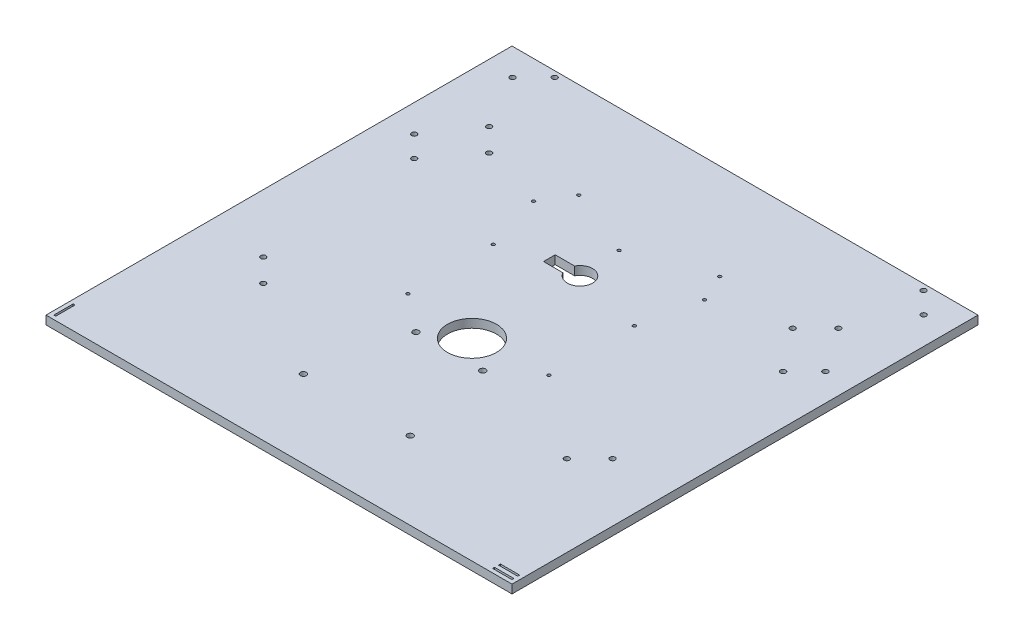
SolidWorks part; units mm, degrees
material "Acrylic (Medium-high impact)"
ref_plane "Front Plane" through (0, 0, 0) normal (0, 0, 1) x (1, 0, 0)
ref_plane "Top Plane" through (0, 0, 0) normal (0, 1, 0) x (1, 0, 0)
ref_plane "Right Plane" through (0, 0, 0) normal (1, 0, 0) x (0, 0, -1)
sketch "Sketch2" plane through (0, 0, 0) normal (0, 1, 0) x (1, 0, 0)
  line L1 (0, 0) -> (304.8, 0)
  line L2 (0, 0) -> (0, 304.8)
  line L3 (0, 304.8) -> (304.8, 304.8)
  line L4 (304.8, 0) -> (304.8, 304.8)
  dimension "D1" = 304.8
  dimension "D2" = 304.8
extrude "Boss-Extrude1" add sketch "Sketch2" along normal blind 5.588
sketch "Sketch4" plane through (0, 5.588, 0) normal (0, 1, 0) x (1, 0, 0)
  line L0 (0, 304.8) -> (0, 0) construction
  line L1 (2.54, 2.54) -> (3.81, 2.54)
  line L2 (2.54, 2.54) -> (2.54, 15.24)
  line L3 (2.54, 15.24) -> (3.81, 15.24)
  line L4 (3.81, 2.54) -> (3.81, 15.24)
  line L5 (2.54, 302.26) -> (3.81, 302.26) construction
  line L6 (2.54, 302.26) -> (2.54, 289.56) construction
  line L7 (2.54, 289.56) -> (3.81, 289.56) construction
  line L8 (3.81, 302.26) -> (3.81, 289.56) construction
  line L9 (6.35, 302.26) -> (7.62, 302.26) construction
  line L10 (6.35, 302.26) -> (6.35, 289.56) construction
  line L11 (6.35, 289.56) -> (7.62, 289.56) construction
  line L12 (7.62, 302.26) -> (7.62, 289.56) construction
  line L13 (304.8, 304.8) -> (0, 304.8) construction
  line L14 (0, 0) -> (304.8, 0) construction
  line L15 (304.8, 0) -> (304.8, 304.8) construction
  line L16 (302.26, 2.54) -> (289.56, 2.54)
  line L17 (302.26, 2.54) -> (302.26, 3.81)
  line L18 (302.26, 3.81) -> (289.56, 3.81)
  line L19 (289.56, 2.54) -> (289.56, 3.81)
  line L20 (302.26, 6.35) -> (289.56, 6.35)
  line L21 (302.26, 6.35) -> (302.26, 7.62)
  line L22 (302.26, 7.62) -> (289.56, 7.62)
  line L23 (289.56, 6.35) -> (289.56, 7.62)
  dimension "D1" = 12.7
  dimension "D2" = 1.27
  dimension "D3" = 2.54
  dimension "D4" = 2.54
  dimension "D5" = 2.54
  dimension "D6" = 2.54
  dimension "D7" = 2.54
  dimension "D8" = 2.54
  dimension "D9" = 2.54
  dimension "D10" = 2.54
extrude "Cut-Extrude1" cut sketch "Sketch4" against normal through all
sketch "Sketch5" plane through (0, 5.588, 0) normal (0, 1, 0) x (1, 0, 0)
  line L0 (0, 304.8) -> (0, 0) construction
  line L1 (34.5465, 268.1122) -> (263.4005, 268.1122)
  line L2 (34.5465, 268.1122) -> (34.5465, 281.0662)
  line L3 (34.5465, 281.0662) -> (263.4005, 281.0662)
  line L4 (263.4005, 268.1122) -> (263.4005, 281.0662)
  line L5 (304.8, 0) -> (304.8, 304.8) construction
  line L6 (304.8, 304.8) -> (0, 304.8) construction
  dimension "D1" = 34.5465
  dimension "D2" = 41.3995
  dimension "D3" = 23.7338
  dimension "D4" = 12.954
extrude "Cut-Extrude2" cut sketch "Sketch5" against normal blind 0.254
sketch "Sketch6" plane through (0, 5.588, 0) normal (0, 1, 0) x (1, 0, 0)
  circle A0 centre (152.48, 126.1263) radius 15.748 construction
  circle A1 centre (152.48, 126.1263) radius 15.748 construction
  circle A2 centre (152.48, 126.1263) radius 16.002
  circle A3 centre (31.75, 300.9596) radius 1.7 construction
  circle A4 centre (17.9388, 287.1483) radius 1.7 construction
  circle A5 centre (273.05, 300.9596) radius 1.7 construction
  circle A6 centre (286.8613, 287.1483) radius 1.7 construction
  circle A7 centre (286.8613, 222.9066) radius 1.7 construction
  circle A8 centre (273.05, 209.0954) radius 1.7 construction
  circle A9 centre (31.75, 209.0954) radius 1.7 construction
  circle A10 centre (17.9388, 222.9066) radius 1.7 construction
  circle A11 centre (31.75, 300.9596) radius 1.7
  circle A12 centre (17.9388, 287.1483) radius 1.7
  circle A13 centre (273.05, 300.9596) radius 1.7
  circle A14 centre (286.8613, 287.1483) radius 1.7
  circle A15 centre (286.8613, 222.9066) radius 1.7
  circle A16 centre (273.05, 209.0954) radius 1.7
  circle A17 centre (31.75, 209.0954) radius 1.7
  circle A18 centre (17.9388, 222.9066) radius 1.7
  circle A19 centre (38.1788, 103.933) radius 1.7 construction
  circle A20 centre (53.133, 88.9788) radius 1.7 construction
  circle A21 centre (251.667, 88.9788) radius 1.7 construction
  circle A22 centre (266.6212, 103.933) radius 1.7 construction
  circle A23 centre (266.6212, 251.667) radius 1.7 construction
  circle A24 centre (251.667, 236.7127) radius 1.7 construction
  circle A25 centre (53.133, 236.7127) radius 1.7 construction
  circle A26 centre (38.1788, 251.667) radius 1.7 construction
  circle A27 centre (38.1788, 103.933) radius 1.7
  circle A28 centre (53.133, 88.9788) radius 1.7
  circle A29 centre (251.667, 88.9788) radius 1.7
  circle A30 centre (266.6212, 103.933) radius 1.7
  circle A31 centre (266.6212, 251.667) radius 1.7
  circle A32 centre (251.667, 236.7127) radius 1.7
  circle A33 centre (53.133, 236.7127) radius 1.7
  circle A34 centre (38.1788, 251.667) radius 1.7
  circle A35 centre (117.555, 50.8216) radius 4.5 construction
  circle A36 centre (187.405, 50.8216) radius 4.5 construction
  circle A37 centre (174.3081, 111.328) radius 4.5 construction
  circle A38 centre (130.6519, 111.328) radius 4.5 construction
  circle A39 centre (117.555, 50.8216) radius 4.5 construction
  circle A40 centre (187.405, 50.8216) radius 4.5 construction
  circle A41 centre (174.3081, 111.328) radius 4.5 construction
  circle A42 centre (130.6519, 111.328) radius 4.5 construction
  circle A43 centre (130.6519, 111.328) radius 1.96
  circle A44 centre (174.3081, 111.328) radius 1.96
  circle A45 centre (187.405, 50.8216) radius 1.96
  circle A46 centre (117.555, 50.8216) radius 1.96
  dimension "D1" = 0.254
  dimension "D2" = 2.54
extrude "Cut-Extrude3" cut sketch "Sketch6" against normal through all
sketch "Sketch7" plane through (0, 5.588, 0) normal (0, 1, 0) x (1, 0, 0)
  line L0 (152.4, 304.8) -> (152.4, 0) construction
  line L1 (304.8, 304.8) -> (0, 304.8) construction
  line L2 (0, 0) -> (304.8, 0) construction
  line L4 (145.0768, 200.66) -> (132.3768, 200.66)
  line L5 (145.0768, 200.66) -> (145.0768, 193.04) construction
  line L6 (145.0768, 193.04) -> (132.3768, 193.04)
  line L7 (132.3768, 200.66) -> (132.3768, 193.04)
  circle A0 centre (152.4, 196.85) radius 8.255 construction
  arc A1 (145.0768, 200.66) -> (145.0768, 193.04) centre (152.4, 196.85) cw
  dimension "D2" = 16.51
  dimension "D1" = 107.95
  dimension "D3" = 7.62
  dimension "D4" = 12.7
extrude "Cut-Extrude4" cut sketch "Sketch7" against normal through all
sketch "Sketch8" plane through (0, 5.588, 0) normal (0, 1, 0) x (1, 0, 0)
  circle A0 centre (94.94, 223.995) radius 0.762 construction
  circle A1 centre (150.82, 223.995) radius 0.762 construction
  circle A2 centre (206.7, 223.995) radius 0.762 construction
  circle A3 centre (94.94, 223.995) radius 0.762 construction
  circle A4 centre (150.82, 223.995) radius 0.762 construction
  circle A5 centre (206.7, 223.995) radius 0.762 construction
  circle A6 centre (206.7, 223.995) radius 1.016
  circle A7 centre (150.82, 223.995) radius 1.016
  circle A8 centre (94.94, 223.995) radius 1.016
  dimension "D1" = 0.254
extrude "Cut-Extrude5" cut sketch "Sketch8" against normal through all
sketch "Sketch9" plane through (0, 5.588, 0) normal (0, 1, 0) x (1, 0, 0)
  circle A0 centre (106.3, 242.18) radius 0.762 construction
  circle A1 centre (106.3, 186.3) radius 0.762 construction
  circle A2 centre (106.3, 130.42) radius 0.762 construction
  circle A3 centre (198.5, 130.42) radius 0.762 construction
  circle A4 centre (198.5, 186.3) radius 0.762 construction
  circle A5 centre (198.5, 242.18) radius 0.762 construction
  circle A6 centre (106.3, 242.18) radius 0.762 construction
  circle A7 centre (106.3, 186.3) radius 0.762 construction
  circle A8 centre (106.3, 130.42) radius 0.762 construction
  circle A9 centre (198.5, 130.42) radius 0.762 construction
  circle A10 centre (198.5, 186.3) radius 0.762 construction
  circle A11 centre (198.5, 242.18) radius 0.762 construction
  circle A12 centre (106.3, 242.18) radius 1.016
  circle A13 centre (106.3, 186.3) radius 1.016
  circle A14 centre (106.3, 130.42) radius 1.016
  circle A15 centre (198.5, 130.42) radius 1.016
  circle A16 centre (198.5, 186.3) radius 1.016
  circle A17 centre (198.5, 242.18) radius 1.016
  dimension "D1" = 0.254
extrude "Cut-Extrude6" cut sketch "Sketch9" against normal through all
sketch "Sketch10" plane through (0, 5.588, 0) normal (0, 1, 0) x (1, 0, 0)
  line L1 (30.0638, 287.1688) -> (266.0755, 287.1688)
  line L2 (30.0638, 287.1688) -> (30.0638, 264.2232)
  line L3 (30.0638, 264.2232) -> (266.0755, 264.2232)
  line L4 (266.0755, 287.1688) -> (266.0755, 264.2232)
extrude "Boss-Extrude3" add sketch "Sketch10" against normal through all
equation "\"D8@Sketch4\"=\"D6@Sketch4\""
